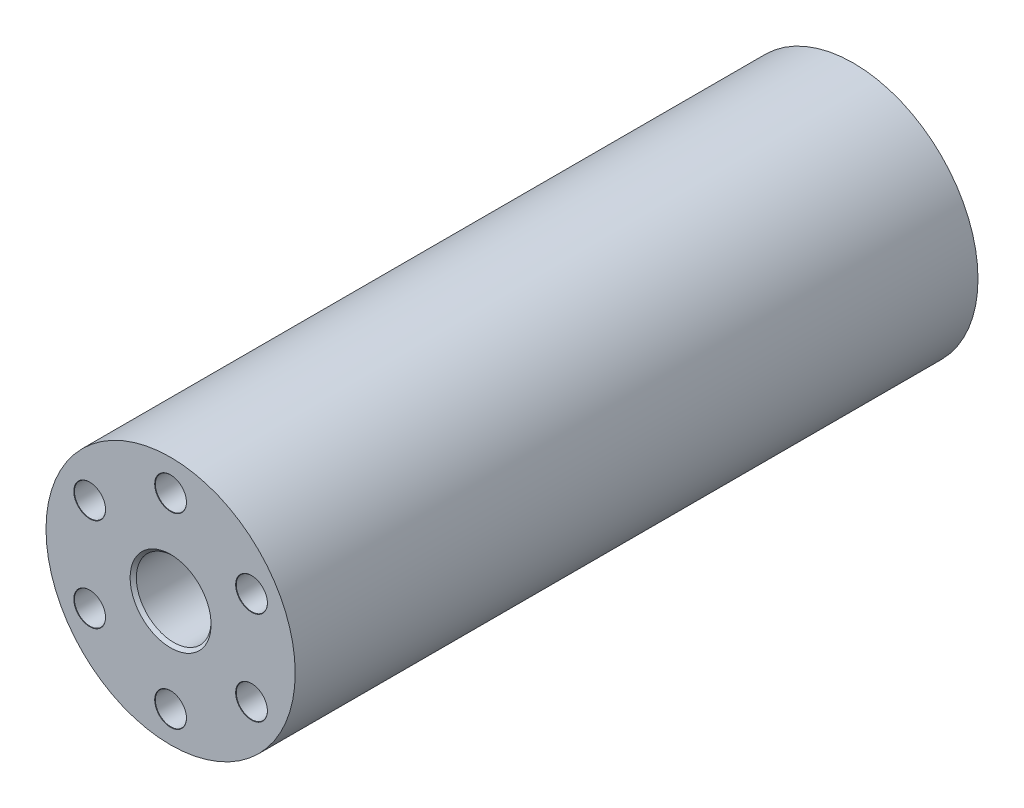
SolidWorks part; units mm, degrees
material "6061-T6 (SS)"
ref_plane "Front Plane" through (0, 0, 0) normal (0, 0, 1) x (1, 0, 0)
ref_plane "Top Plane" through (0, 0, 0) normal (0, 1, 0) x (1, 0, 0)
ref_plane "Right Plane" through (0, 0, 0) normal (1, 0, 0) x (0, 0, -1)
sketch "Sketch1" plane through (0, 0, 0) normal (0, 0, 1) x (1, 0, 0)
  circle A0 centre (0, 0) radius 10
  dimension "D1" = 20
extrude "Boss-Extrude1" add sketch "Sketch1" along normal blind 54.8
sketch "Sketch2" plane through (0, 0, 0) normal (0, 0, 1) x (1, 0, 0)
  point P0 (0, 0)
hole_wizard "Ø6.0mm Dowel Hole1" positions "Sketch2" profile "Sketch4" hole size "Ø6.0" standard "DIN" end condition through all
sketch "Sketch4" plane through (0, 0, 0) normal (1, 0, 0) x (0, 1, 0)
  line L0 (0, 0) -> (0, 54.8)
  line L1 (0, 54.8) -> (3.25, 54.8)
  line L2 (3, 54.55) -> (3, 0.25)
  line L3 (3, 0.25) -> (3.25, 0)
  line L5 (3.25, 0) -> (0, 0)
  line L6 (-3, 0.25) -> (-3.25, 0) construction
  line L7 (3.25, 54.8) -> (3, 54.55)
  line L8 (-3.25, 54.8) -> (-3, 54.55) construction
  line L11 (0, -6.35) -> (0, 107.95) construction
  dimension "Thru Hole Dia." = 6
  dimension "Thru Hole Depth" = 54.8
  dimension "Near C'Sink Dia." = 6.5
  dimension "Near C'Sink Angle" = 90
  dimension "Far C'Sink Dia." = 6.5
  dimension "Far C'Sink Angle" = 90
sketch "Sketch5" plane through (0, 0, 0) normal (0, 0, -1) x (-1, 0, 0)
  circle A0 centre (0, 0) radius 7
  point P6 (0, 7)
  point P10 (6.0622, -3.5)
  point P11 (-6.0622, -3.5)
  dimension "D1" = 14
  dimension "D2" = 3
hole_wizard "Tap Drill for M3 Tap1" positions "Sketch5" profile "Sketch6" hole size "M3" standard "DIN"
sketch "Sketch6" plane through (6.0622, -3.5, 0) normal (1, 0, 0) x (0, 1, 0)
  line L0 (0, 0) -> (0, 10.7511)
  line L1 (0, 10.7511) -> (1.25, 10)
  line L2 (1.25, 10) -> (1.25, 0.025)
  line L3 (1.25, 0.025) -> (1.275, 0)
  line L5 (1.275, 0) -> (0, 0)
  line L6 (-1.25, 0.025) -> (-1.275, 0) construction
  line L10 (0, 10.7511) -> (-1.25, 10) construction
  line L11 (0, -6.35) -> (0, 107.95) construction
  dimension "Hole Dia." = 2.5
  dimension "Hole Depth" = 10
  dimension "Near C'Sink Dia." = 2.55
  dimension "Near C'Sink Angle" = 90
  dimension "Drill Angle" = 118
sketch "Sketch7" plane through (0, 0, 54.8) normal (0, 0, 1) x (1, 0, 0)
  line L0 (0, 3) -> (0, 12) construction
  circle A0 centre (0, 0) radius 3 construction
  circle A2 centre (0, 0) radius 12 construction
  circle A4 centre (0, 0) radius 7.5 construction
  point P20 (0, 7.5)
  point P24 (6.4952, 3.75)
  point P25 (6.4952, -3.75)
  point P26 (0, -7.5)
  point P27 (-6.4952, -3.75)
  point P28 (-6.4952, 3.75)
  point P34 (0, 7.5)
  dimension "D1" = 15
  dimension "D2" = 6
hole_wizard "Tap Drill for M3 Tap2" positions "Sketch7" profile "Sketch9" hole size "M3" standard "DIN"
sketch "Sketch9" plane through (-6.4952, 3.75, 54.8) normal (1, 0, 0) x (0, -1, 0)
  line L0 (0, 0) -> (0, 10.7511)
  line L1 (0, 10.7511) -> (1.25, 10)
  line L2 (1.25, 10) -> (1.25, 0.025)
  line L3 (1.25, 0.025) -> (1.275, 0)
  line L5 (1.275, 0) -> (0, 0)
  line L6 (-1.25, 0.025) -> (-1.275, 0) construction
  line L10 (0, 10.7511) -> (-1.25, 10) construction
  line L11 (0, -6.35) -> (0, 107.95) construction
  dimension "Hole Dia." = 2.5
  dimension "Hole Depth" = 10
  dimension "Near C'Sink Dia." = 2.55
  dimension "Near C'Sink Angle" = 90
  dimension "Drill Angle" = 118
